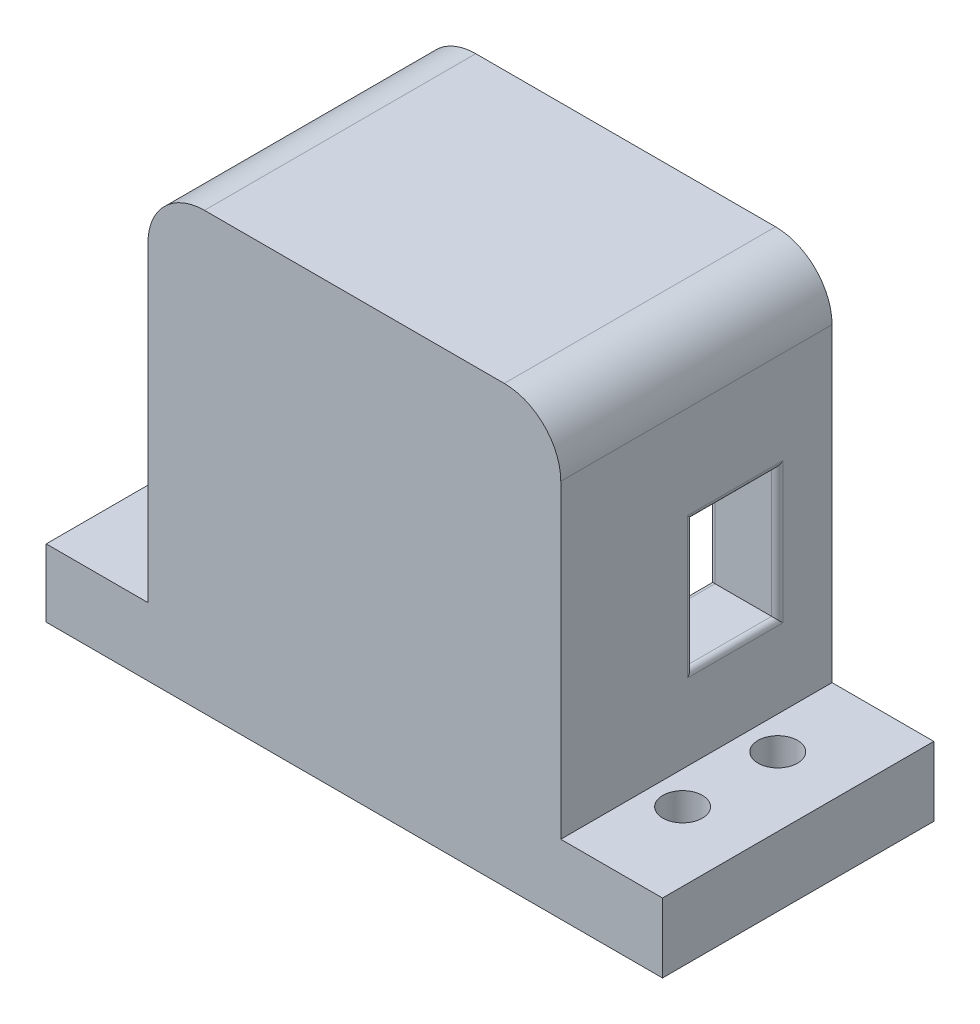
SolidWorks part; units mm, degrees
ref_plane "Front Plane" through (0, 0, 0) normal (0, 0, 1) x (1, 0, 0)
ref_plane "Top Plane" through (0, 0, 0) normal (0, 1, 0) x (1, 0, 0)
ref_plane "Right Plane" through (0, 0, 0) normal (1, 0, 0) x (0, 0, -1)
sketch "Sketch1" plane through (0, 0, 0) normal (0, 0, 1) x (1, 0, 0)
  line L0 (27.2067, 44.5538) -> (27.2067, 37.5587) construction
  line L1 (-0.0534, 6) -> (14.9466, 6)
  line L2 (-0.0534, 6) -> (-0.0534, 12)
  line L3 (-0.0534, 12) -> (8.9466, 12)
  line L6 (14.9466, 6) -> (14.9466, 37.5587)
  line L8 (8.9466, 12) -> (8.9466, 41.5587)
  line L9 (15.2067, 44.5538) -> (39.2067, 44.5538)
  line L11 (14.9466, 37.5587) -> (39.4668, 37.5587)
  line L14 (45.4668, 12.1289) -> (45.4668, 41.5587)
  line L15 (39.2067, 44.5538) -> (42.4668, 44.5538)
  line L16 (39.4668, 6) -> (39.4668, 37.5587)
  line L18 (54.4668, 12.1289) -> (45.4668, 12.1289)
  line L19 (54.4668, 6) -> (54.4668, 12.1289)
  line L20 (54.4668, 6) -> (39.4668, 6)
  line L21 (8.9466, 41.5587) -> (8.9466, 44.5538)
  line L22 (8.9466, 44.5538) -> (15.2067, 44.5538)
  line L23 (42.4668, 44.5538) -> (45.4668, 44.5538)
  line L24 (29.343, 6) -> (34.3809, 6) construction
  line L25 (45.4668, 44.5538) -> (45.4668, 41.5587)
  dimension "D1" = 9
  dimension "D2" = 6
  dimension "D3" = 12
  dimension "D6" = 6
extrude "Boss-Extrude1" add sketch "Sketch1" along normal blind 17.5
sketch "Sketch2" plane through (0, 0, 17.5) normal (0, 0, 1) x (1, 0, 0)
  line L0 (8.9466, 12) -> (8.9466, 44.5538)
  line L1 (8.9466, 44.5538) -> (45.4668, 44.5538)
  line L2 (45.4668, 44.5538) -> (45.4668, 6)
  line L3 (39.4668, 6) -> (54.4668, 6) construction
  line L4 (45.4668, 6) -> (8.9466, 6)
  line L5 (-0.0534, 6) -> (14.9466, 6) construction
  line L6 (8.9466, 6) -> (8.9466, 12)
extrude "Boss-Extrude2" add sketch "Sketch2" along normal blind 6.5
sketch "Sketch4" plane through (0, 0, 17.5) normal (0, 0, -1) x (-1, 0, 0)
  line L1 (-39.4668, 37.5587) -> (-14.9466, 37.5587)
  line L2 (-39.4668, 37.5587) -> (-39.4668, 6)
  line L3 (-39.4668, 6) -> (-14.9466, 6)
  line L4 (-14.9466, 37.5587) -> (-14.9466, 6)
extrude "Cut-Extrude1" cut sketch "Sketch4" against normal blind 3.5
sketch "Sketch5" plane through (0, 0, 21) normal (0, 0, -1) x (-1, 0, 0)
  line L0 (-45.4668, 44.5538) -> (-8.9466, 44.5538) construction
  line L1 (-39.4668, 37.5587) -> (-14.9466, 37.5587)
  line L2 (-39.4668, 37.5587) -> (-39.4668, 42.0038)
  line L3 (-39.4668, 42.0038) -> (-14.9466, 42.0038)
  line L4 (-14.9466, 37.5587) -> (-14.9466, 42.0038)
  dimension "D1" = 2.55
extrude "Cut-Extrude2" cut sketch "Sketch5" along normal blind 4.5
fillet "Fillet1" radius 5 2 edges at (8.9466, 44.5538, 12) (45.4668, 44.5538, 12)
sketch "Sketch7" plane through (0, 0, 17.5) normal (0, 0, 1) x (1, 0, 0)
  line L1 (-0.0534, 12) -> (8.9466, 12)
  line L2 (-0.0534, 12) -> (-0.0534, 6)
  line L3 (-0.0534, 6) -> (8.9466, 6)
  line L4 (8.9466, 12) -> (8.9466, 6)
  line L5 (45.4668, 12.1289) -> (54.4668, 12.1289)
  line L6 (45.4668, 12.1289) -> (45.4668, 6)
  line L7 (45.4668, 6) -> (54.4668, 6)
  line L8 (54.4668, 12.1289) -> (54.4668, 6)
extrude "Boss-Extrude3" add sketch "Sketch7" along normal through all
sketch "Sketch6" plane through (0, 12.1289, 0) normal (0, 1, 0) x (1, 0, 0)
  line L1 (8.9466, 0) -> (-0.0534, 0) construction
  circle A0 centre (48.3647, -16.12) radius 1.75
  circle A1 centre (48.3647, -7.7) radius 1.75
  circle A2 centre (5.9447, -16.12) radius 1.75
  circle A3 centre (5.9447, -7.7) radius 1.75
  dimension "D1" = 3.5
  dimension "D4" = 42.42
  dimension "D2" = 8.42
  dimension "D3" = 42.42
  dimension "D5" = 7.7
extrude "Cut-Extrude3" cut sketch "Sketch6" against normal up to next
fillet "Fillet2" radius 1 2 edges at (39.4668, 21.7793, 0) (14.9466, 21.7793, 0)
sketch "Sketch8" plane through (8.9466, 0, 0) normal (-1, 0, 0) x (0, 0, 1)
  line L1 (4.8522, 30.818) -> (12.4455, 30.818)
  line L2 (4.8522, 30.818) -> (4.8522, 19.2363)
  line L3 (4.8522, 19.2363) -> (12.4455, 19.2363)
  line L4 (12.4455, 30.818) -> (12.4455, 19.2363)
extrude "Cut-Extrude4" cut sketch "Sketch8" against normal up to next
fillet "Fillet3" radius 0.5 10 edges at (11.9466, 19.2363, 12.4455) (8.9466, 19.2363, 8.6489) (11.9466, 19.2363, 4.8522) (8.9466, 25.0272, 4.8522) (8.9466, 25.0272, 12.4455) (8.9466, 30.818, 8.6489) (14.9466, 30.818, 8.6489) (14.9466, 19.2363, 8.6489) (14.9466, 25.0272, 12.4455) (14.9466, 25.0272, 4.8522)
sketch "Sketch9" plane through (45.4668, 0, 0) normal (1, 0, 0) x (0, 0, -1)
  line L0 (-4.8522, 30.818) -> (-4.8522, 19.7363) construction
  line L1 (-12.2991, 30.818) -> (-4.8522, 30.818)
  line L2 (-12.2991, 30.818) -> (-12.2991, 19.3827)
  line L3 (-12.2991, 19.3827) -> (-4.8522, 19.3827)
  line L4 (-4.8522, 30.818) -> (-4.8522, 19.3827)
  line L5 (-12.4455, 30.818) -> (-4.8522, 30.818) construction
  arc A0 (-12.4455, 19.7363) -> (-11.9455, 19.2363) centre (-11.9455, 19.7363) ccw construction
  point P4 (-12.2991, 19.3827)
  point P8 (-4.8522, 30.818)
  point P13 (-12.4455, 30.818)
extrude "Cut-Extrude5" cut sketch "Sketch9" against normal up to next
fillet "Fillet4" radius 0.5 8 edges at (39.4668, 30.818, 8.5756) (39.4668, 19.3827, 8.5756) (39.4668, 25.1004, 12.2991) (39.4668, 25.1004, 4.8522) (45.4668, 25.1004, 12.2991) (45.4668, 19.3827, 8.5756) (45.4668, 25.1004, 4.8522) (45.4668, 30.818, 8.5756)
